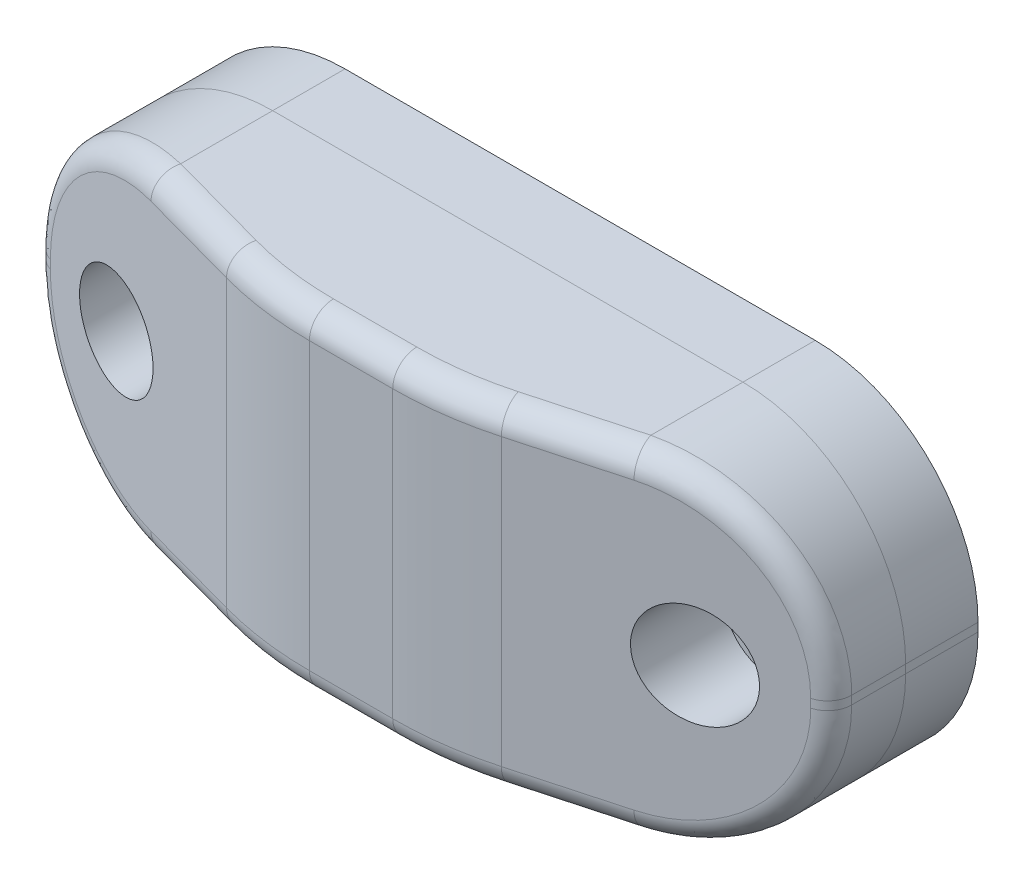
SolidWorks part; units mm, degrees
material "Custom Plastic"
ref_plane "X-Y Datum" through (0, 0, 0) normal (0, 0, 1) x (1, 0, 0)
ref_plane "X-Z Datum" through (0, 0, 0) normal (0, 1, 0) x (1, 0, 0)
ref_plane "Y-Z Datum" through (0, 0, 0) normal (1, 0, 0) x (0, 0, -1)
sketch "Sketch1" plane through (0, 0, 0) normal (0, 0, 1) x (1, 0, 0)
  line L0 (-24, 0) -> (24, 0) construction
  line L1 (-19.5, 13.85) -> (19.5, 13.85)
  line L2 (-33, 0.35) -> (-33, -0.35)
  line L3 (-19.5, -13.85) -> (19.5, -13.85)
  line L4 (33, 0.35) -> (33, -0.35)
  line L5 (-33, 13.85) -> (33, -13.85) construction
  line L6 (-33, -13.85) -> (33, 13.85) construction
  circle A0 centre (-24, 0) radius 2.3
  circle A1 centre (24, 0) radius 2.3
  arc A2 (19.5, 13.85) -> (33, 0.35) centre (19.5, 0.35) cw
  arc A3 (19.5, -13.85) -> (33, -0.35) centre (19.5, -0.35) ccw
  arc A4 (-19.5, 13.85) -> (-33, 0.35) centre (-19.5, 0.35) ccw
  arc A5 (-33, -0.35) -> (-19.5, -13.85) centre (-19.5, -0.35) ccw
  point P0 (0, 0)
  point P9 (0, 0)
  dimension "D4" = 4.6
  dimension "D5" = 13.5
  dimension "D1" = 27.7
  dimension "D2" = 66
  dimension "D3" = 48
extrude "Boss-Extrude1" add sketch "Sketch1" along normal blind 19
sketch "Sketch2" plane through (0, -13.85, 0) normal (0, -1, 0) x (1, 0, 0)
  line L0 (19.5, 0) -> (33, 0) construction
  line L1 (33, 0) -> (33, 19) construction
  line L2 (33, 19) -> (19.5, 19) construction
  line L3 (-19.5, 0) -> (19.5, 0) construction
  line L4 (19.5, 19) -> (-19.5, 19) construction
  line L5 (-33, 0) -> (-19.5, 0) construction
  line L6 (-19.5, 19) -> (-33, 19) construction
  line L7 (-33, 19) -> (-33, 0) construction
  line L8 (19.5, 0) -> (33, 0)
  line L9 (33, 0) -> (33, 19)
  line L10 (33, 19) -> (19.5, 19)
  line L11 (-19.5, 0) -> (19.5, 0)
  line L12 (19.5, 19) -> (-19.5, 19)
  line L13 (-33, 0) -> (-19.5, 0)
  line L14 (-19.5, 19) -> (-33, 19)
  line L15 (-33, 19) -> (-33, 0)
  line L16 (-33, 12) -> (-7.5, 19)
  line L17 (-7.5, 19) -> (7.5, 19)
  line L18 (0, -10.45) -> (0, 10.45) construction
  line L19 (33, 12) -> (7.5, 19)
  point P13 (0, 19)
  line M11 (19.5, 0) -> (19.5, 19)
  line M12 (19.5, 19) -> (-19.5, 19)
  line M13 (-19.5, 19) -> (-19.5, 0)
  dimension "D1" = 12
  dimension "D2" = 15
extrude "Cut-Extrude1" cut sketch "Sketch2" against normal through all contours L16 L12 M13 | L15 L16 L14 M13 | L19 M11 M12 | L19 L9 L10 M11 region at (27.06, -13.85, 16.3153) region at (15.5, -13.85, 17.902) region at (-15.5, -13.85, 17.902) region at (-27.06, -13.85, 16.3153)
fillet "Fillet1" radius 30 2 edges at (7.5, 0, 19) (-7.5, 0, 19)
fillet "Fillet2" radius 2 16 edges at (-29.0459, -9.8959, 13.0854) (-33, 0, 12) (-29.0459, 9.8959, 13.0854) (-15.4493, 13.85, 16.8178) (-7.4638, 13.85, 18.7312) (0, 13.85, 19) (7.4638, 13.85, 18.7312) (15.4493, 13.85, 16.8178) (29.0459, 9.8959, 13.0854) (33, 0, 12) (29.0459, -9.8959, 13.0854) (15.4493, -13.85, 16.8178) (7.4638, -13.85, 18.7312) (0, -13.85, 19) (-7.4638, -13.85, 18.7312) (-15.4493, -13.85, 16.8178)
sketch "Sketch3" plane through (0, 0, 19) normal (0, 0, 1) x (1, 0, 0)
  circle A0 centre (-24, 0) radius 4.2
  circle A1 centre (24, 0) radius 4.2
  dimension "D1" = 8.4
extrude "Cut-Extrude2" cut sketch "Sketch3" against normal offset from surface (11 mm away) 8 up to face at (-21.7, 0, 0)
sketch "Sketch4" plane through (0, 0, 0) normal (0, 0, -1) x (-1, 0, 0)
  line L1 (-4.5, 6.5) -> (4.5, 6.5)
  line L2 (-4.5, 6.5) -> (-4.5, -6.5)
  line L3 (-4.5, -6.5) -> (4.5, -6.5)
  line L4 (4.5, 6.5) -> (4.5, -6.5)
  line L5 (-4.5, 6.5) -> (4.5, -6.5) construction
  line L6 (-4.5, -6.5) -> (4.5, 6.5) construction
  point P0 (0, 0)
  dimension "D1" = 9
  dimension "D2" = 13
extrude "Boss-Extrude2" add sketch "Sketch4" along normal blind 1
ref_plane "Plane1" through (0, 0, 6) normal (0, 0, -1) x (-1, 0, 0)
split line "Split Line1"
